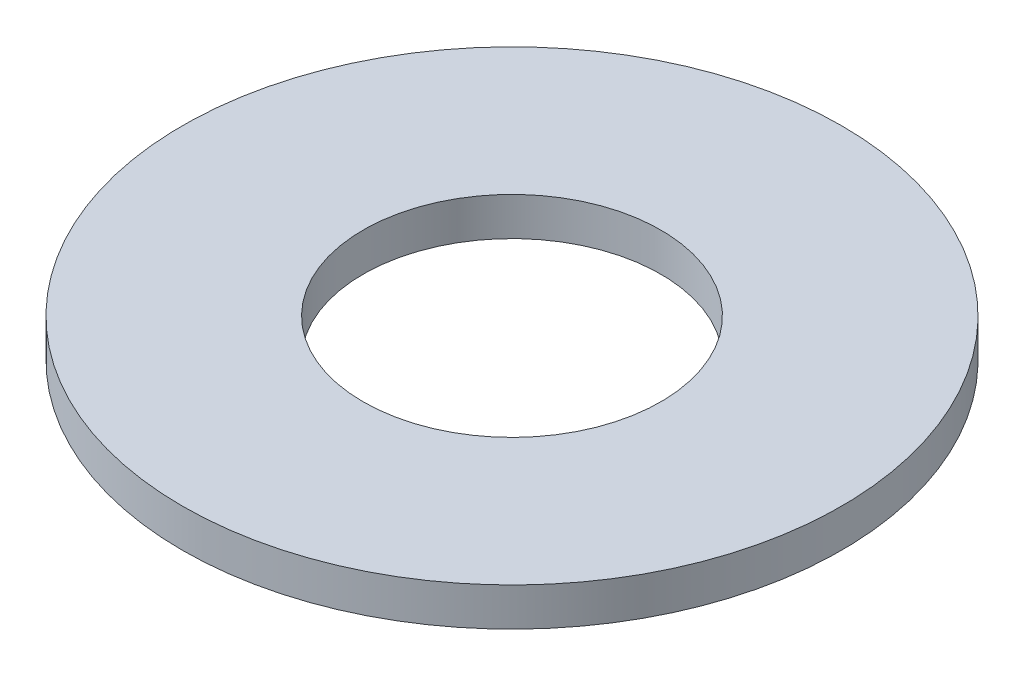
SolidWorks part; units mm, degrees
ref_plane "Front Plane" through (0, 0, 0) normal (0, 0, 1) x (1, 0, 0)
ref_plane "Top Plane" through (0, 0, 0) normal (0, 1, 0) x (1, 0, 0)
ref_plane "Right Plane" through (0, 0, 0) normal (1, 0, 0) x (0, 0, -1)
sketch "Sketch1" plane through (0, 0, 0) normal (0, 1, 0) x (1, 0, 0)
  circle A0 centre (0, 0) radius 77.5
  dimension "FLANGE_OD" = 155
extrude "Boss-Extrude1" add sketch "Sketch1" along normal blind 9
sketch "Sketch2" plane through (0, 0, 0) normal (0, 1, 0) x (1, 0, 0)
  circle A0 centre (0, 0) radius 35
  dimension "BORE_D" = 70
extrude "Cut-Extrude1" cut sketch "Sketch2" along normal through all
sketch "Sketch3" plane through (0, 9, 0) normal (0, 1, 0) x (1, 0, 0)
  circle A0 centre (0, 0) radius 22.2501 construction
  circle A1 centre (-22.2501, 0) radius 5.2492
  dimension "BOLT_D" = 10.4985
  dimension "BOLT_PCD" = 44.5003
extrude "Cut-Extrude2" cut sketch "Sketch3" against normal blind 6.5924 rebuild error yes
pattern_circular "CirPattern1" count 8 over 360 rebuild error yes
